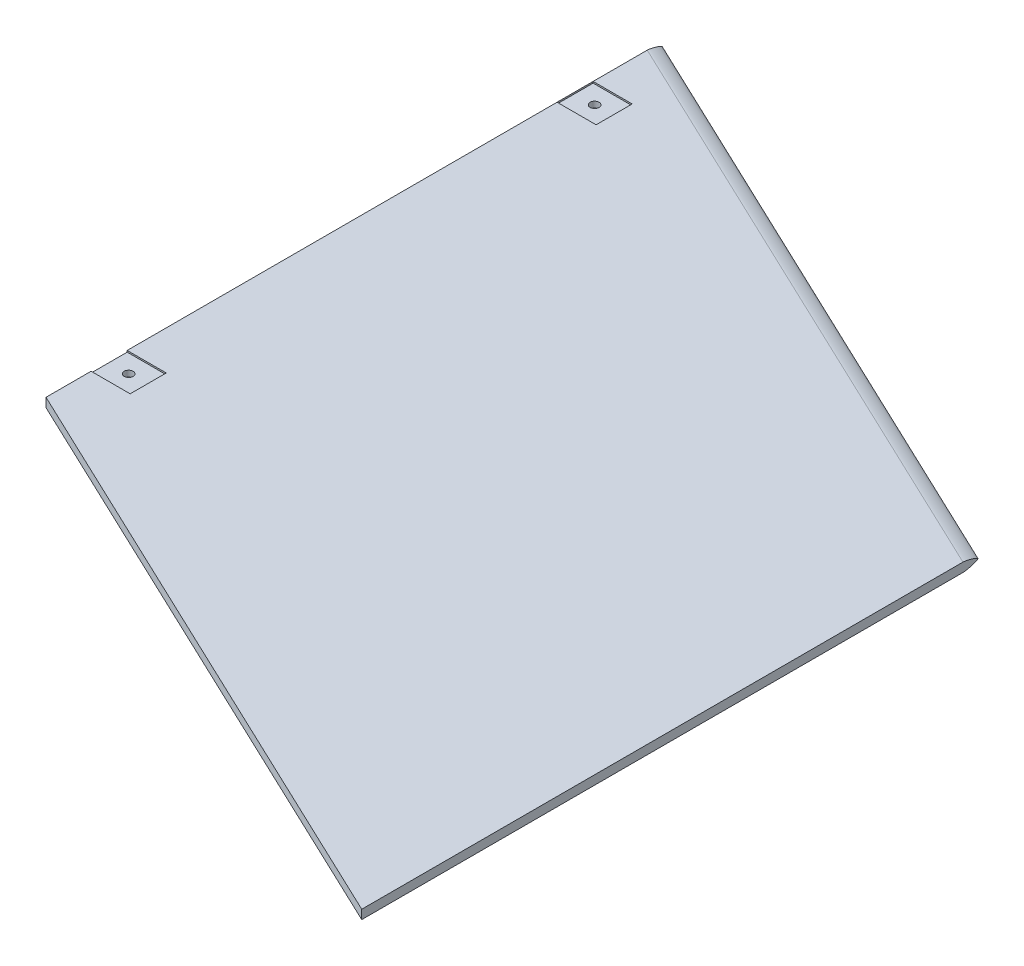
SolidWorks part; units mm, degrees
ref_plane "Front Plane" through (0, 0, 0) normal (0, 0, 1) x (1, 0, 0)
ref_plane "Top Plane" through (0, 0, 0) normal (0, 1, 0) x (1, 0, 0)
ref_plane "Right Plane" through (0, 0, 0) normal (1, 0, 0) x (0, 0, -1)
sketch "Sketch1" plane through (0, 0, 0) normal (0, 1, 0) x (1, 0, 0)
  line L0 (0, 200) -> (0, 0)
  line L1 (0, 0) -> (200, -94.967)
  line L2 (200, -94.967) -> (200, 105.033)
  line L3 (200, 105.033) -> (0, 200)
  dimension "D1" = 200
  dimension "D2" = 200
  dimension "D3" = 200
  dimension "D4" = 64.6
extrude "Boss-Extrude1" add sketch "Sketch1" along normal mid plane 3
sketch "Sketch2" plane through (0, 0, 0) normal (0, 0, 1) x (1, 0, 0)
  line L0 (0, -1.5) -> (0, 1.5)
  arc A0 (0, -1.5) -> (0, 1.5) centre (-20.1944, 0) ccw
  dimension "D1" = 20.25
sketch "Sketch3" plane through (0, 0, 0) normal (-1, 0, 0) x (0, 0, 1)
  line L0 (-55.5588, 0) -> (-32.3372, 0) construction
  line L1 (-200, 1.5) -> (-200, -1.5)
  spline S0 degree 4 poles (-205, 0) (-204.9997, 0.0016) (-204.9989, 0.0039) (-204.9972, 0.0073) (-204.994, 0.0128) (-204.9892, 0.0198) (-204.9807, 0.0307) (-204.9656, 0.0472) (-204.9397, 0.0718) (-204.8963, 0.1077) (-204.8257, 0.1584) (-204.7231, 0.2231) (-204.56, 0.3142) (-204.3411, 0.4216) (-204.077, 0.5372) (-203.7743, 0.6563) (-203.4682, 0.7663) (-203.0822, 0.8941) (-202.6146, 1.0335) (-202.1425, 1.1569) (-201.6667, 1.2649) (-201.2678, 1.3437) (-200.9473, 1.3995) (-200.6256, 1.447) (-200.3484, 1.479) (-200.1513, 1.4947) (-200.035, 1.4996) (-200, 1.5) knots 0 0 0 0 0 0.001215 0.001853 0.002907 0.004743 0.007643 0.012328 0.019818 0.031794 0.050229 0.078089 0.111622 0.173183 0.234744 0.296305 0.357866 0.419426 0.542548 0.66567 0.727231 0.788791 0.850352 0.911913 0.973474 1 1 1 1 1 construction
  spline S1 degree 4 poles (-205, 0) (-204.9997, 0.0016) (-204.9989, 0.0039) (-204.9972, 0.0073) (-204.994, 0.0128) (-204.9892, 0.0198) (-204.9807, 0.0307) (-204.9656, 0.0472) (-204.9397, 0.0718) (-204.8963, 0.1077) (-204.8257, 0.1584) (-204.7231, 0.2231) (-204.56, 0.3142) (-204.3411, 0.4216) (-204.077, 0.5372) (-203.7743, 0.6563) (-203.4682, 0.7663) (-203.0822, 0.8941) (-202.6146, 1.0335) (-202.1425, 1.1569) (-201.6667, 1.2649) (-201.2678, 1.3437) (-200.9473, 1.3995) (-200.6256, 1.447) (-200.3484, 1.479) (-200.1513, 1.4947) (-200.035, 1.4996) (-200, 1.5) knots 0 0 0 0 0 0.001215 0.001853 0.002907 0.004743 0.007643 0.012328 0.019818 0.031794 0.050229 0.078089 0.111622 0.173183 0.234744 0.296305 0.357866 0.419426 0.542548 0.66567 0.727231 0.788791 0.850352 0.911913 0.973474 1 1 1 1 1
  spline S2 degree 4 poles (-205, 0) (-204.9997, -0.0016) (-204.9989, -0.0039) (-204.9972, -0.0073) (-204.994, -0.0128) (-204.9892, -0.0198) (-204.9807, -0.0307) (-204.9656, -0.0472) (-204.9397, -0.0718) (-204.8963, -0.1077) (-204.8257, -0.1584) (-204.7231, -0.2231) (-204.56, -0.3142) (-204.3411, -0.4216) (-204.077, -0.5372) (-203.7743, -0.6563) (-203.4682, -0.7663) (-203.0822, -0.8941) (-202.6146, -1.0335) (-202.1425, -1.1569) (-201.6667, -1.2649) (-201.2678, -1.3437) (-200.9473, -1.3995) (-200.6256, -1.447) (-200.3484, -1.479) (-200.1513, -1.4947) (-200.035, -1.4996) (-200, -1.5) knots 0 0 0 0 0 0.001215 0.001853 0.002907 0.004743 0.007643 0.012328 0.019818 0.031794 0.050229 0.078089 0.111622 0.173183 0.234744 0.296305 0.357866 0.419426 0.542548 0.66567 0.727231 0.788791 0.850352 0.911913 0.973474 1 1 1 1 1
sweep "Sweep1" add profiles "Sketch3" path edge at (100, 1.5, -152.5165)
sketch "Sketch4" plane through (0, 1.5, 0) normal (0, 1, 0) x (1, 0, 0)
  line L0 (0.0001, 199.9999) -> (0, 0) construction
  line L1 (0.0001, 181.9999) -> (13.0001, 181.9999)
  line L2 (0.0001, 181.9999) -> (0.0001, 169.9999)
  line L3 (0.0001, 169.9999) -> (13.0001, 169.9999)
  line L4 (13.0001, 181.9999) -> (13.0001, 169.9999)
  line L7 (0, 15) -> (13, 15)
  line L8 (0, 15) -> (0, 27)
  line L9 (0, 27) -> (13, 27)
  line L10 (13, 15) -> (13, 27)
  dimension "D1" = 12
  dimension "D2" = 13
  dimension "D3" = 18
  dimension "D4" = 15
extrude "Cut-Extrude1" cut sketch "Sketch4" against normal blind 0.5
sketch "Sketch5" plane through (0, 1, 0) normal (0, 1, 0) x (1, 0, 0)
  line L0 (13.0001, 181.9999) -> (0.0001, 181.9999) construction
  line L1 (13.0001, 169.9999) -> (13.0001, 181.9999) construction
  line L2 (13, 27) -> (0, 27) construction
  line L3 (13, 15) -> (13, 27) construction
  circle A0 centre (6.5001, 175.9999) radius 1.5
  circle A1 centre (6.5, 21) radius 1.5
  point P5 (6.5001, 181.9999)
  point P9 (13.0001, 175.9999)
  point P13 (6.5, 27)
  point P17 (13, 21)
  dimension "D1" = 3
extrude "Cut-Extrude2" cut sketch "Sketch5" against normal through all
mirror "Mirror1" about plane through (0, 0, 0) normal (0, 1, 0) of "Cut-Extrude1"
